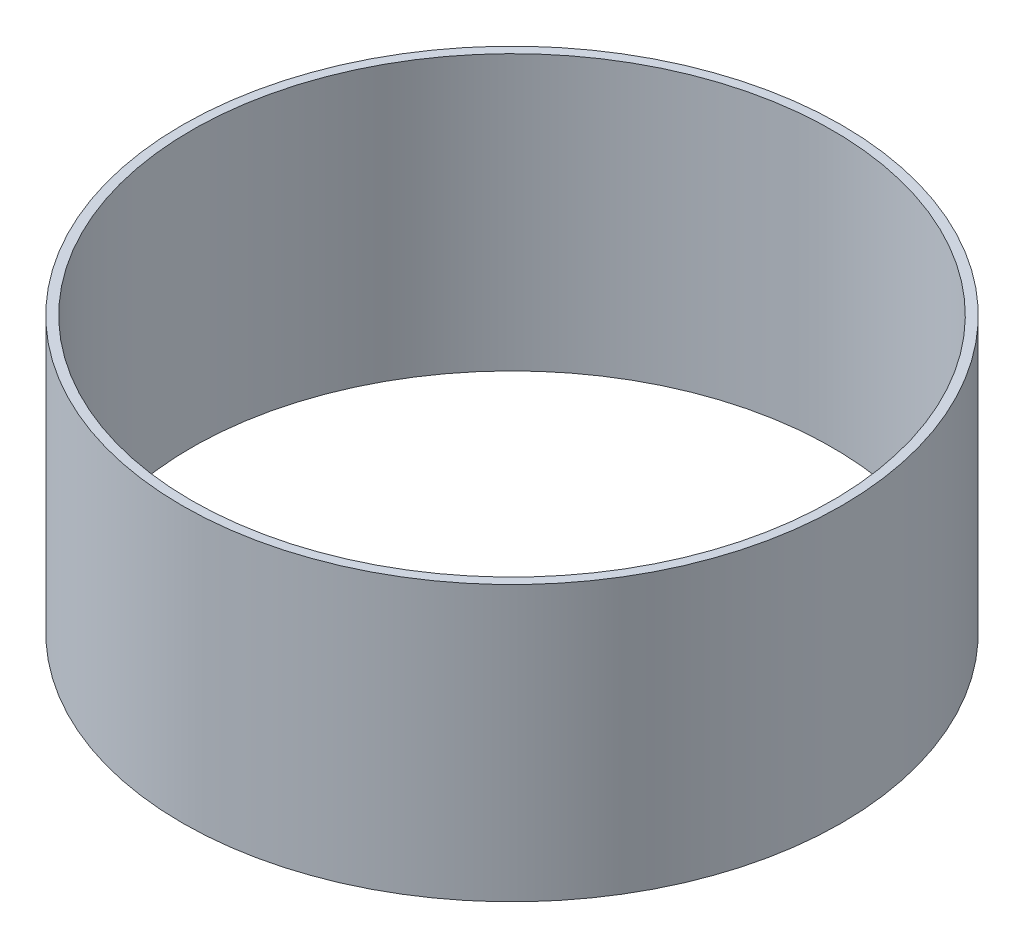
SolidWorks part; units mm, degrees
ref_plane "Front Plane" through (0, 0, 0) normal (0, 0, 1) x (1, 0, 0)
ref_plane "Top Plane" through (0, 0, 0) normal (0, 1, 0) x (1, 0, 0)
ref_plane "Right Plane" through (0, 0, 0) normal (1, 0, 0) x (0, 0, -1)
sketch "Sketch1" plane through (0, 0, 0) normal (0, 1, 0) x (1, 0, 0)
  circle A0 centre (0, 0) radius 35
  circle A1 centre (0, 0) radius 36
  dimension "D1" = 70
  dimension "D2" = 1
extrude "Boss-Extrude1" add sketch "Sketch1" along normal blind 30
